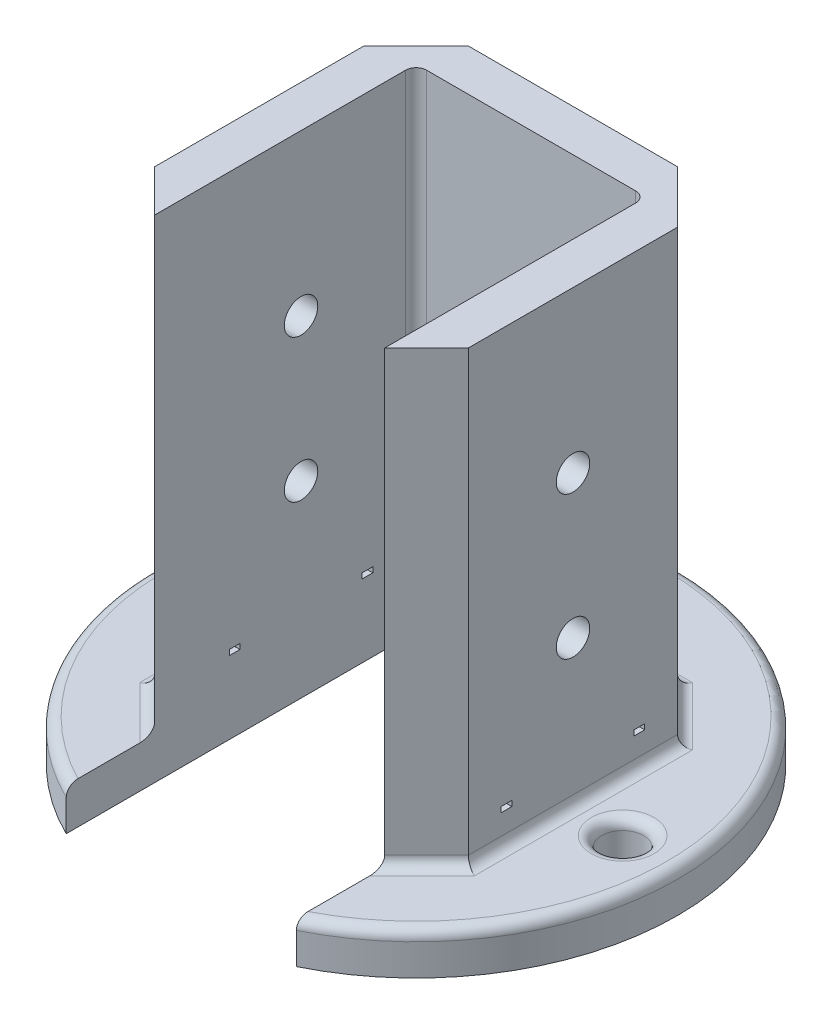
SolidWorks part; units mm, degrees
ref_plane "Front Plane" through (0, 0, 0) normal (0, 0, 1) x (1, 0, 0)
ref_plane "Top Plane" through (0, 0, 0) normal (0, 1, 0) x (1, 0, 0)
ref_plane "Right Plane" through (0, 0, 0) normal (1, 0, 0) x (0, 0, -1)
sketch "Sketch1" plane through (0, 0, 0) normal (0, 1, 0) x (1, 0, 0)
  line L1 (0, 0) -> (30, 0)
  line L2 (0, 0) -> (0, 30)
  line L3 (0, 30) -> (30, 30)
  line L4 (30, 0) -> (30, 30)
  dimension "D1" = 30
  dimension "D2" = 30
extrude "Boss-Extrude1" add sketch "Sketch1" along normal blind 62
shell "Shell1" thickness 4 removed face at (15, 0, -15) removed face at (15, 62, -15)
sketch "Sketch2" plane through (30, 0, 0) normal (1, 0, 0) x (0, 0, -1)
  line L0 (0, 0) -> (30, 0) construction
  circle A0 centre (15, 14) radius 1.6
  circle A2 centre (15, 27.66) radius 1.6
  point P4 (15, 26.06)
  point P7 (15, 15.6)
  point P8 (15, 0)
  dimension "D1" = 3.2
  dimension "D2" = 3.2
  dimension "D3" = 10.46
  dimension "D4" = 14
extrude "Cut-Extrude1" cut sketch "Sketch2" against normal blind 62
sketch "Sketch3" plane through (0, 0, 0) normal (0, -1, 0) x (1, 0, 0)
  line L0 (26, -26) -> (4, -26) construction
  line L9 (30, 0) -> (30, -30) construction
  line L11 (26, -4) -> (26, -26) construction
  line L12 (4, -26) -> (4, -4) construction
  line L13 (4, -4) -> (26, -4) construction
  line L14 (26, -26) -> (4, -26)
  line L15 (26, -4) -> (26, -26)
  line L16 (4, -26) -> (4, -4)
  line L17 (4, -4) -> (26, -4)
  circle A0 centre (15, -15) radius 25
  circle A1 centre (34.75, -15) radius 2
  circle A8 centre (15, -34.75) radius 2
  circle A9 centre (-4.75, -15) radius 2
  circle A10 centre (15, 4.75) radius 2
  point P7 (26, -15)
  point P15 (15, -26)
  point P23 (16.25, -11.25)
  point P24 (15, -15)
  dimension "D1" = 50
  dimension "D2" = 4
  dimension "D3" = 4.75
  dimension "D4" = 4
extrude "Boss-Extrude2" add sketch "Sketch3" along normal blind 4
pattern_circular "CirPattern1" count 2 over 90 about axis through (15, -4, -15) along (0, 1, 0) of "Cut-Extrude1"
chamfer "Chamfer1" distance 5 angle 45 4 edges at (0, 31, 0) (30, 31, 0) (30, 31, -30) (0, 31, -30)
fillet "Fillet1" radius 1 12 edges at (15, 62, -4) (26, 62, -15) (15, 62, -26) (4, 62, -15) (2.5, 62, -27.5) (15, 62, -30) (27.5, 62, -27.5) (30, 62, -15) (27.5, 62, -2.5) (15, 62, 0) (2.5, 62, -2.5) (0, 62, -15)
fillet "Fillet2" radius 1 13 edges at (34.75, 0, -17) (15, 0, -40) (2.5, 0, -2.5) (15, 0, 0) (27.5, 0, -2.5) (30, 0, -15) (27.5, 0, -27.5) (15, 0, -30) (2.5, 0, -27.5) (0, 0, -15) (15, 0, 2.75) (-4.75, 0, -17) (15, 0, -36.75)
sketch "Sketch4" plane through (4, 0, 0) normal (1, 0, 0) x (0, 0, -1)
  line L0 (8.14, 3.46) -> (9.16, 3.46)
  line L1 (9.16, 3.46) -> (9.16, 2.95)
  line L2 (9.16, 2.95) -> (8.14, 2.95)
  line L3 (8.14, 2.95) -> (8.14, 3.46)
  line L12 (21.86, 2.95) -> (21.86, 3.46)
  line L13 (21.86, 3.46) -> (20.84, 3.46)
  line L14 (20.84, 3.46) -> (20.84, 2.95)
  line L15 (20.84, 2.95) -> (21.86, 2.95)
extrude "Cut-Extrude2" cut sketch "Sketch4" against normal through all both and the other way through all
pattern_circular "CirPattern2" count 2 over 90 about axis through (15, -4, -15) along (0, -1, 0) of "Cut-Extrude2"
sketch "Sketch5" plane through (0, 62, 0) normal (0, 1, 0) x (1, 0, 0)
  line L1 (4, 4) -> (26, 4)
  line L2 (4, 4) -> (4, -10.9141)
  line L3 (4, -10.9141) -> (26, -10.9141)
  line L4 (26, 4) -> (26, -10.9141)
extrude "Cut-Extrude3" cut sketch "Sketch5" against normal through all
sketch "Sketch6" plane through (0, 0, 0) normal (-1, 0, 0) x (0, 0, 1)
  line L0 (-5, 1) -> (-5, 61) construction
  line L1 (-25, 58) -> (-5, 58)
  line L2 (-25, 58) -> (-25, 43)
  line L3 (-25, 43) -> (-5, 43)
  line L4 (-5, 58) -> (-5, 43)
  line L5 (-5, 61) -> (-25, 61) construction
  dimension "D1" = 18
  dimension "D2" = 3
extrude "Cut-Extrude4" cut sketch "Sketch6" against normal through all and the other way through all
sketch "Sketch7" plane through (0, 0, -30) normal (0, 0, -1) x (-1, 0, 0)
  line L0 (-5, 1) -> (-5, 61) construction
  line L1 (-25, 58) -> (-5, 58)
  line L2 (-25, 58) -> (-25, 43)
  line L3 (-25, 43) -> (-5, 43)
  line L4 (-5, 58) -> (-5, 43)
  line L5 (-5, 61) -> (-25, 61) construction
  dimension "D1" = 18
  dimension "D2" = 3
extrude "Cut-Extrude5" cut sketch "Sketch7" against normal through all contours L1 L4 L3 L2
fillet "Fillet4" radius 1 12 edges at (2, 43, -5) (2, 58, -5) (2, 58, -25) (2, 43, -25) (25, 43, -28) (25, 58, -28) (28, 58, -25) (28, 43, -25) (5, 43, -28) (5, 58, -28) (28, 58, -5) (28, 43, -5)
sketch "Sketch8" plane through (0, 0, 0) normal (-1, 0, 0) x (0, 0, 1)
  line L1 (-34.6564, 43) -> (5.0381, 43)
  line L2 (-34.6564, 43) -> (-34.6564, 63.9454)
  line L3 (-34.6564, 63.9454) -> (5.0381, 63.9454)
  line L4 (5.0381, 43) -> (5.0381, 63.9454)
extrude "Cut-Extrude6" cut sketch "Sketch8" against normal through all
fillet "Fillet5" radius 1 2 edges at (26, 19.5, -26) (4, 19.5, -26)
